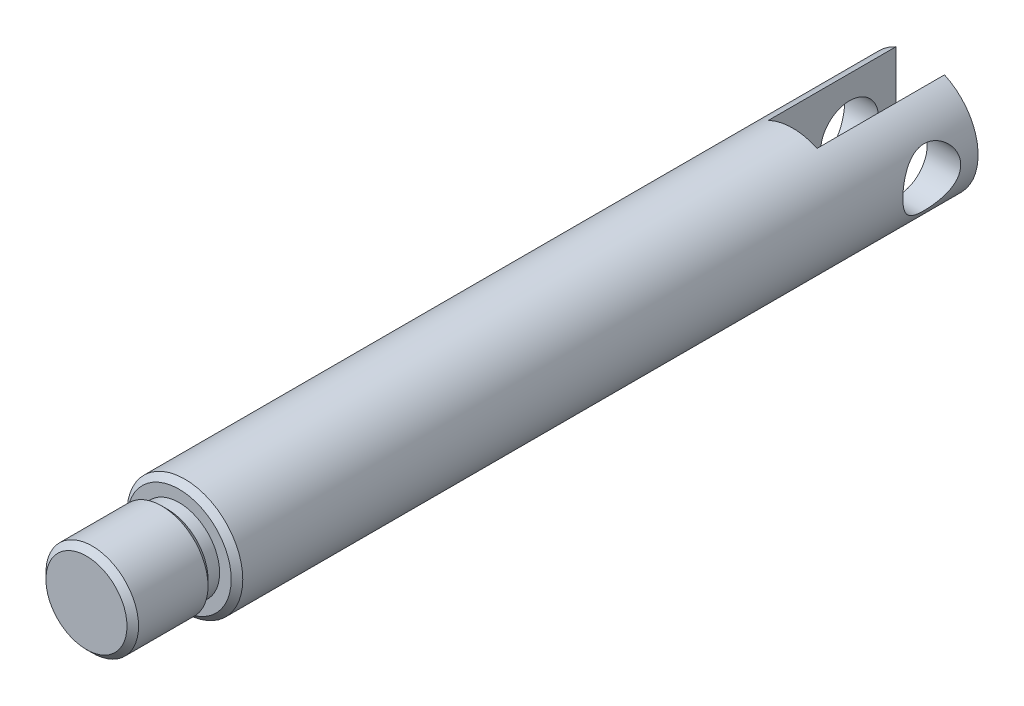
SolidWorks part; units mm, degrees
material "Stainless Steel (ferritic)"
ref_plane "Front Plane" through (0, 0, 0) normal (0, 0, 1) x (1, 0, 0)
ref_plane "Top Plane" through (0, 0, 0) normal (0, 1, 0) x (1, 0, 0)
ref_plane "Right Plane" through (0, 0, 0) normal (1, 0, 0) x (0, 0, -1)
sketch "Sketch1" plane through (0, 0, 0) normal (0, 0, 1) x (1, 0, 0)
  circle A0 centre (0, 0) radius 2.5
  dimension "D1" = 5
extrude "Boss-Extrude1" add sketch "Sketch1" along normal blind 32
sketch "Sketch2" plane through (0, 0, 32) normal (0, 0, 1) x (1, 0, 0)
  circle A0 centre (0, 0) radius 1.75
  dimension "D1" = 3.5
extrude "Boss-Extrude2" add sketch "Sketch2" along normal blind 0.5
sketch "Sketch4" plane through (0, 0, 32.5) normal (0, 0, 1) x (1, 0, 0)
  circle A0 centre (0, 0) radius 2
  dimension "D1" = 4
extrude "Boss-Extrude3" add sketch "Sketch4" along normal blind 3.5
chamfer "Chamfer1" distance 0.25 angle 45 3 edges at (2.5, 0, 32) (2, 0, 32.5) (2, 0, 36)
sketch "Sketch5" plane through (0, 0, 0) normal (1, 0, 0) x (0, 0, -1)
  line L0 (0, -2.5) -> (0, 2.5) construction
  circle A0 centre (-2, 0) radius 1.25
  dimension "D1" = 2.5
  dimension "D2" = 2
extrude "Cut-Extrude1" cut sketch "Sketch5" against normal through all both and the other way through all
sketch "Sketch6" plane through (0, 0, 0) normal (0, 1, 0) x (1, 0, 0)
  line L0 (2.5, 0) -> (-2.5, 0) construction
  line L1 (-1.05, 0) -> (1.05, 0)
  line L2 (-1.05, 0) -> (-1.05, -5.5)
  line L3 (-1.05, -5.5) -> (1.05, -5.5)
  line L4 (1.05, 0) -> (1.05, -5.5)
  dimension "D1" = 2.1
  dimension "D2" = 1.05
  dimension "D3" = 5.5
extrude "Cut-Extrude2" cut sketch "Sketch6" against normal through all both and the other way through all
